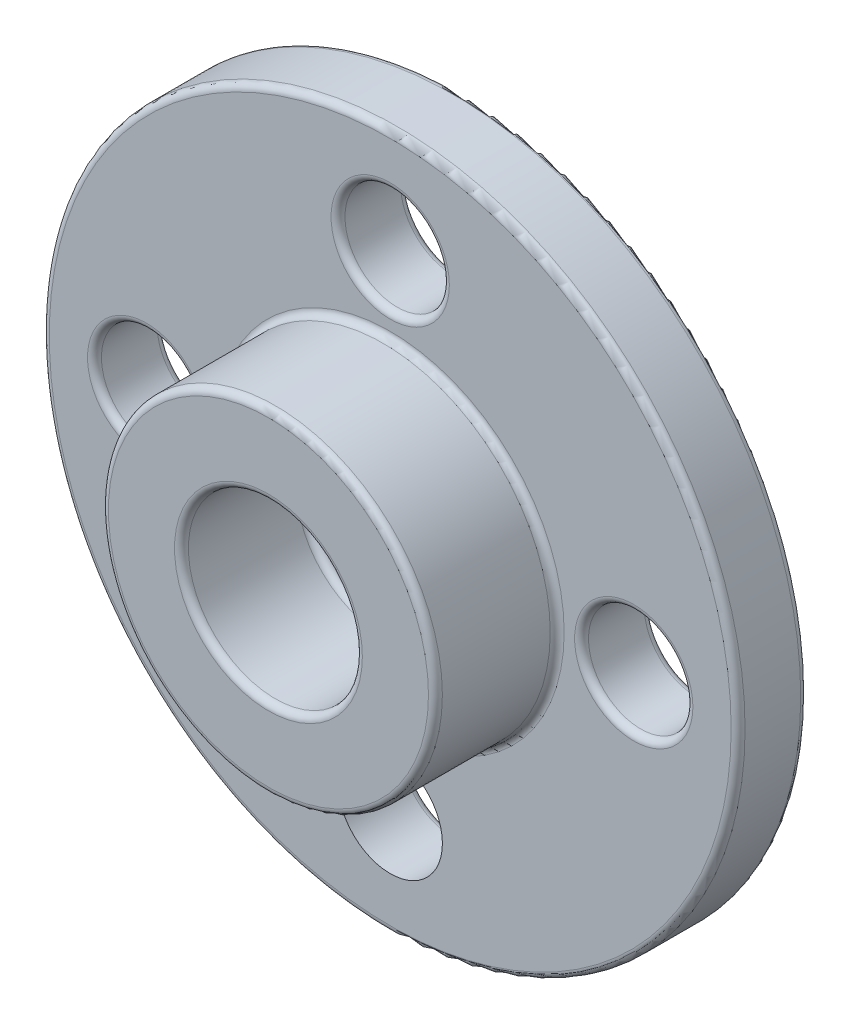
SolidWorks part; units mm, degrees
ref_plane "前视基准面" through (0, 0, 0) normal (0, 0, 1) x (1, 0, 0)
ref_plane "上视基准面" through (0, 0, 0) normal (0, 1, 0) x (1, 0, 0)
ref_plane "右视基准面" through (0, 0, 0) normal (1, 0, 0) x (0, 0, -1)
sketch "草图2" plane through (0, 0, 0) normal (0, 0, 1) x (1, 0, 0)
  circle A0 centre (0, 0) radius 4.8
  circle A1 centre (0, 0) radius 7 construction
  circle A2 centre (0, 0) radius 10
  circle A3 centre (0, 0) radius 2.5
  circle A4 centre (0, 7) radius 1.5
  circle A5 centre (7, 0) radius 1.5
  circle A6 centre (0, -7) radius 1.5
  circle A7 centre (-7, 0) radius 1.5
  circle A8 centre (0, 0) radius 1.65
  point P17 (0, 0)
  dimension "D1" = 5
  dimension "D2" = 9.6
  dimension "D3" = 14
  dimension "D4" = 20
  dimension "D5" = 4
  dimension "D6" = 3
  dimension "D7" = 3.3
extrude "凸台-拉伸1" add sketch "草图2" along normal blind 2 contours A3 A8 | A2 A7 A6 A5 A4 A0 region at (-9.7172, 0, 0) region at (-2.4293, 0, 0)
cosmetic thread "装饰螺纹线1" parameters "D2"=9
cosmetic thread "装饰螺纹线2" parameters "D2"=9
cosmetic thread "装饰螺纹线3" parameters "D2"=9
cosmetic thread "装饰螺纹线4" parameters "D2"=9
extrude "凸台-拉伸2" add sketch "草图2<4>" along normal blind 5.5 contours A0 A3 region at (-4.6642, 0, 0)
sketch "草图2<4>" plane through (0, 0, 0) normal (0, 0, 1) x (1, 0, 0) same geometry as "草图2"
fillet "圆角1" radius 0.2 15 edges at (8.5, 0, 2) (-5.5, 0, 2) (1.5, 7, 2) (10, 0, 2) (4.8, 0, 2) (1.65, 0, 2) (2.5, 0, 2) (2.5, 0, 5.5) (-5.5, 0, 0) (1.5, 7, 0) (8.5, 0, 0) (1.5, -7, 0) (1.65, 0, 0) (10, 0, 0) (4.8, 0, 5.5)
